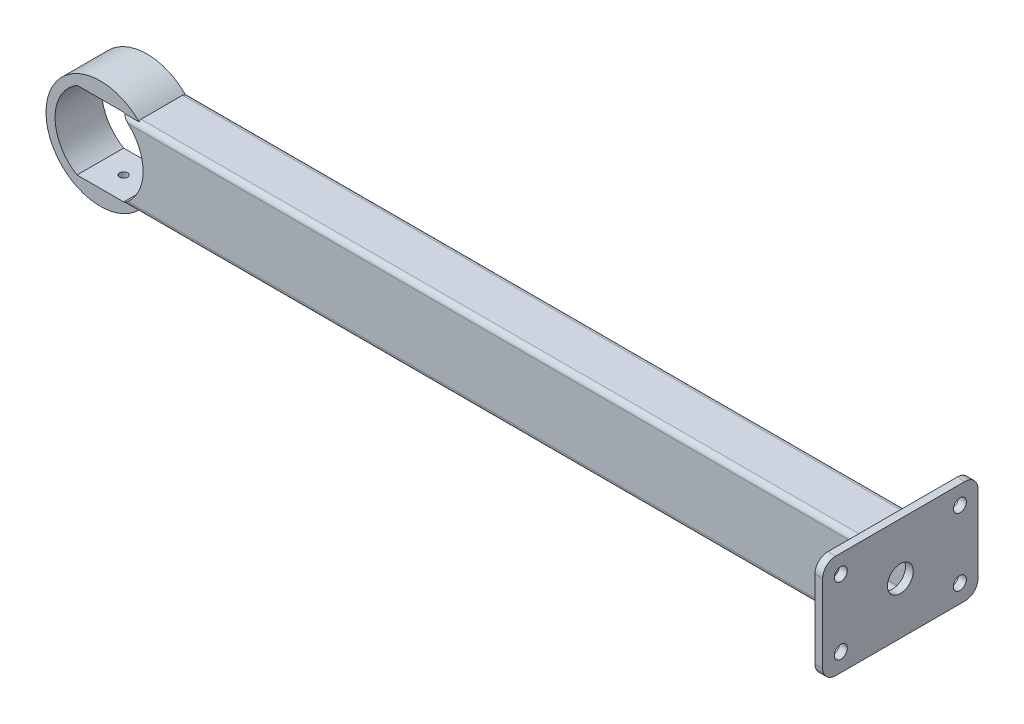
SolidWorks part; units mm, degrees
ref_plane "Front Plane" through (0, 0, 0) normal (0, 0, 1) x (1, 0, 0)
ref_plane "Top Plane" through (0, 0, 0) normal (0, 1, 0) x (1, 0, 0)
ref_plane "Right Plane" through (0, 0, 0) normal (1, 0, 0) x (0, 0, -1)
sketch "Sketch2" plane through (0, 0, 0) normal (1, 0, 0) x (0, 0, -1)
  line L1 (-7, 14) -> (7, 14)
  line L2 (-9, 12) -> (-9, -12)
  line L3 (-7, -14) -> (7, -14)
  line L4 (9, 12) -> (9, -12)
  line L5 (-9, 14) -> (9, -14) construction
  line L6 (-9, -14) -> (9, 14) construction
  line L7 (-8, 15) -> (8, 15)
  line L8 (-10, 13) -> (-10, -13)
  line L9 (-8, -15) -> (8, -15)
  line L10 (10, 13) -> (10, -13)
  line L11 (-10, 15) -> (10, -15) construction
  line L12 (-10, -15) -> (10, 15) construction
  arc A0 (8, 15) -> (10, 13) centre (8, 13) cw
  arc A1 (-8, 15) -> (-10, 13) centre (-8, 13) ccw
  arc A2 (-8, -15) -> (-10, -13) centre (-8, -13) cw
  arc A3 (8, -15) -> (10, -13) centre (8, -13) ccw
  arc A4 (9, -12) -> (7, -14) centre (7, -12) cw
  arc A5 (-7, -14) -> (-9, -12) centre (-7, -12) cw
  arc A6 (-9, 12) -> (-7, 14) centre (-7, 12) cw
  arc A7 (7, 14) -> (9, 12) centre (7, 12) cw
  point P0 (0, 0)
  point P1 (0, 0)
  point P7 (0, 0)
  dimension "D5" = 2
  dimension "D1" = 30
  dimension "D2" = 20
  dimension "D3" = 18
  dimension "D4" = 28
extrude "Boss-Extrude1" add sketch "Sketch2" along normal blind 300
ref_plane "Sketch8" through (300, 0, 0) normal (1, 0, 0) x (0, 0, -1)
sketch "Sketch9" plane through (300, 0, 0) normal (1, 0, 0) x (0, 0, -1)
  line L1 (-30, -20) -> (30, -20)
  line L2 (0, -20) -> (0, 20)
  line L3 (-30, 20) -> (30, 20)
  line L4 (30, -20) -> (30, 20)
  line L5 (0, 0) -> (41.0566, 0) construction
  line L6 (23, 40.0805) -> (23, -47.0797) construction
  line L7 (-30, -20) -> (-30, 20)
  circle A0 centre (23, 13) radius 2.5
  circle A1 centre (23, -13) radius 2.5
  circle A2 centre (0, 0) radius 5
  circle A3 centre (-23, -13) radius 2.5
  circle A4 centre (-23, 13) radius 2.5
  point P9 (23, 0)
  point P12 (23, 0)
  point P13 (23, 13)
  point P14 (23, -13)
  dimension "D3" = 30
  dimension "D4" = 23
  dimension "D5" = 13
  dimension "D6" = 13
extrude "Boss-Extrude2" add sketch "Sketch9" against normal blind 3 contours A2 L2 L1 L4 L3 A1 A0 | A2 L2 L3 L7 L1 A3 A4 region at (300, 0, 15.1708) region at (300, 0, -15.1708)
sketch "Sketch10" plane through (0, 0, 0) normal (0, 0, 1) x (1, 0, 0)
  line L1 (0, 13) -> (0, -13) construction
  line L2 (0, 0) -> (0, 19.4509) construction
  line L3 (0, 19.4509) -> (0, -17.2685) construction
  line L4 (9.0139, -15) -> (-9.0139, -15)
  line L5 (9.0139, 15) -> (-9.0139, 15)
  circle A0 centre (0, 0) radius 21
  circle A1 centre (0, 0) radius 17.5
  point P0 (0, 0)
  point P6 (0, 15)
  point P10 (0, -15)
  dimension "D1" = 42
  dimension "D2" = 35
  dimension "D3" = 15
  dimension "D4" = 15
extrude "Boss-Extrude3" add sketch "Sketch10" along normal blind 9 and the other way blind 9 contours L5 A1 | A0 A1 | L4 A1 region at (0, -16.0064, 0) region at (0, 16.0064, 0) region at (-20.406, 0, 0)
extrude "Cut-Extrude1" cut sketch "Sketch10<3>" against normal blind 19 and the other way blind 19 contours L5 A1 L4 region at (0, 0, 0)
sketch "Sketch10<3>" plane through (0, 0, 0) normal (0, 0, 1) x (1, 0, 0) same geometry as "Sketch10"
hole_wizard "Ø3.0mm Dowel Hole1" positions "Sketch11" profile "Sketch12" hole size "Ø3.0" standard "ISO"
sketch "Sketch11" plane through (0, -15, 0) normal (0, 1, 0) x (1, 0, 0)
  point P0 (0, 0)
sketch "Sketch12" plane through (0, -15, 0) normal (1, 0, 0) x (0, 0, 1)
  line L0 (0, 0) -> (0, 8.4013)
  line L1 (0, 8.4013) -> (1.5, 7.5)
  line L2 (1.5, 7.5) -> (1.5, 0.025)
  line L3 (1.5, 0.025) -> (1.525, 0)
  line L5 (1.525, 0) -> (0, 0)
  line L6 (-1.5, 0.025) -> (-1.525, 0) construction
  line L10 (0, 8.4013) -> (-1.5, 7.5) construction
  line L11 (0, -6.35) -> (0, 107.95) construction
  dimension "Hole Dia." = 3
  dimension "Hole Depth" = 7.5
  dimension "Near C'Sink Dia." = 3.05
  dimension "Near C'Sink Angle" = 90
  dimension "Drill Angle" = 118
fillet "Fillet1" radius 5 4 edges at (298.5, 20, 30) (298.5, -20, 30) (298.5, -20, -30) (298.5, 20, -30)
